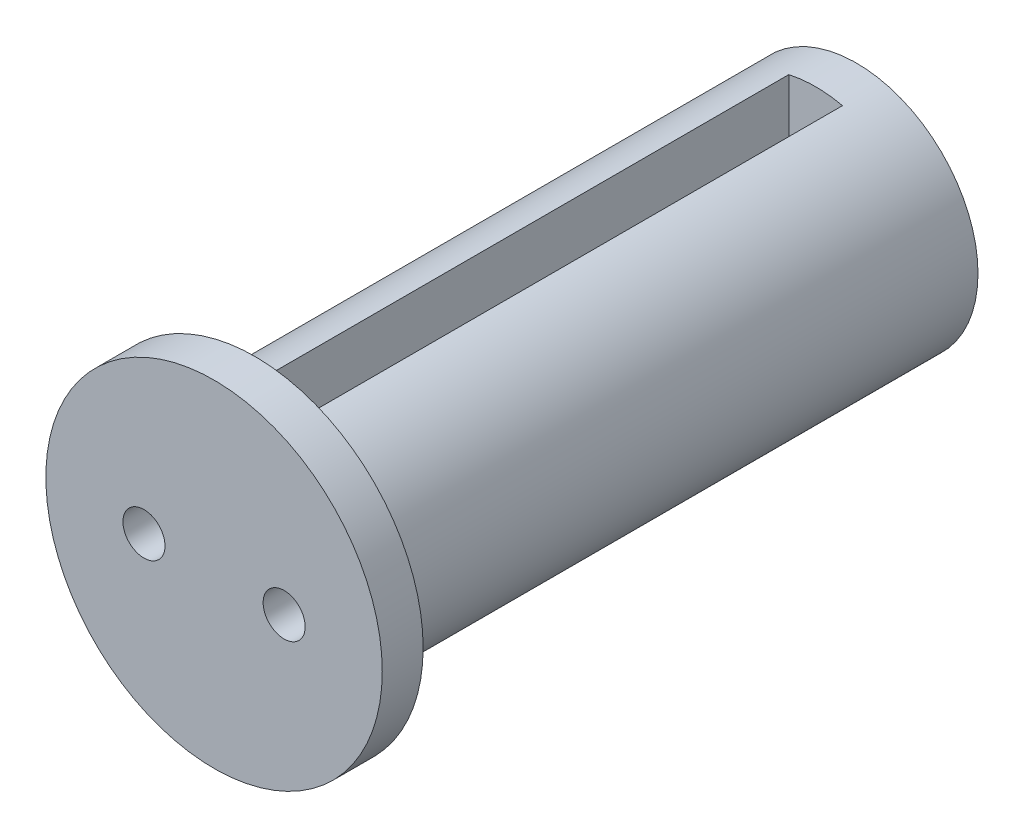
SolidWorks part; units mm, degrees
ref_plane "前视基准面" through (0, 0, 0) normal (0, 0, 1) x (1, 0, 0)
ref_plane "上视基准面" through (0, 0, 0) normal (0, 1, 0) x (1, 0, 0)
ref_plane "右视基准面" through (0, 0, 0) normal (1, 0, 0) x (0, 0, -1)
sketch "草图1" plane through (0, 0, 0) normal (0, 0, 1) x (1, 0, 0)
  circle A0 centre (0, 0) radius 5.2
extrude "凸台-拉伸1" add sketch "草图1" along normal blind 27.5
ref_plane "基准面4" through (0, 0, 13.75) normal (0, 0, 1) x (1, 0, 0)
sketch "草图2" plane through (0, 0, 13.75) normal (0, 0, 1) x (1, 0, 0)
  line L0 (-1.15, -2) -> (1.15, -2)
  line L2 (1.15, -2) -> (1.15, 6)
  line L3 (1.15, 6) -> (-1.15, 6)
  line L4 (-1.15, -2) -> (-1.15, 6)
  line L5 (0, 0) -> (0, 1.2264) construction
  point P0 (0, 0)
  dimension "D1" = 2.3
  dimension "D2" = 6
  dimension "D3" = 2
extrude "切除-拉伸1" cut sketch "草图2" against normal mid plane 24
sketch "草图3" plane through (0, 0, 27.5) normal (0, 0, 1) x (1, 0, 0)
  line L0 (0, 0) -> (0, 5.6384) construction
  circle A0 centre (-3, 0) radius 0.85
  circle A1 centre (3, 0) radius 0.85
  point P9 (0, 0)
  dimension "D1" = 1.7
  dimension "D2" = 3
  dimension "D3" = 2
sketch "草图6" plane through (0, 0, 27.5) normal (0, 0, 1) x (1, 0, 0)
  circle A0 centre (0, 0) radius 7.2
extrude "凸台-拉伸3" add sketch "草图6" against normal blind 1.75
extrude "切除-拉伸4" cut sketch "草图3" against normal blind 8
mirror "镜向3" about plane through (0, 0, 13.75) normal (0, 0, 1) of "切除-拉伸4"
sketch "草图7" plane through (0, 0, 27.5) normal (0, 0, 1) x (1, 0, 0)
  circle A0 centre (-3, 0) radius 0.9
  circle A1 centre (3, 0) radius 0.9
extrude "切除-拉伸5" cut sketch "草图7" against normal up to surface (8 mm away) up to face at (-2.15, 0, 19.5)
